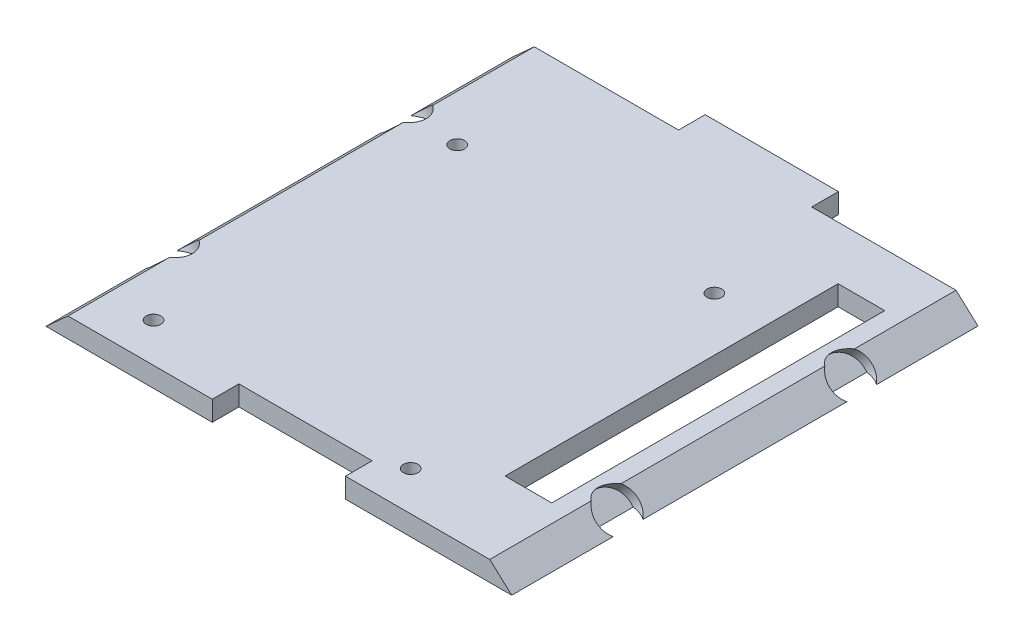
SolidWorks part; units mm, degrees
ref_plane "Front Plane" through (0, 0, 0) normal (0, 0, 1) x (1, 0, 0)
ref_plane "Top Plane" through (0, 0, 0) normal (0, 1, 0) x (1, 0, 0)
ref_plane "Right Plane" through (0, 0, 0) normal (1, 0, 0) x (0, 0, -1)
sketch "Sketch1" plane through (0, 0, 0) normal (0, 0, 1) x (1, 0, 0)
  line L0 (0, 0) -> (0, 44.45) construction
  line L1 (-40.2039, 5.9378) -> (40.2039, 5.9378)
  line L2 (-44.399, 2.1278) -> (44.399, 2.1278)
  line L3 (-40.2039, 5.9378) -> (-44.399, 2.1278)
  line L4 (40.2039, 5.9378) -> (44.399, 2.1278)
  arc A0 (44.399, 2.1278) -> (-44.399, 2.1278) centre (0, 0) ccw construction
  arc A1 (40.2039, 5.9378) -> (-40.2039, 5.9378) centre (0, 0) ccw construction
  dimension "D1" = 88.9
  dimension "D2" = 3.81
  dimension "D3" = 3.81
extrude "Boss-Extrude1" add sketch "Sketch1" along normal blind 88.9
sketch "Sketch2" plane through (0, 2.1278, 0) normal (0, -1, 0) x (1, 0, 0)
  line L0 (0, 88.9) -> (0, 0) construction
  line L1 (-34.417, 85.09) -> (20.701, 85.09) construction
  line L2 (-34.417, 85.09) -> (-34.417, 0) construction
  line L3 (-34.417, 0) -> (20.701, 0) construction
  line L4 (20.701, 85.09) -> (20.701, 0) construction
  line L5 (-44.399, 88.9) -> (44.399, 88.9) construction
  line L6 (-44.399, 0) -> (44.399, 0) construction
  line L7 (-34.417, 42.545) -> (20.701, 42.545) construction
  line L8 (-6.858, 85.09) -> (-6.858, 0) construction
  circle A0 centre (-31.369, 81.43) radius 1.397
  circle A1 centre (17.653, 23.518) radius 1.397
  circle A2 centre (-31.369, 23.518) radius 1.397
  circle A3 centre (17.653, 81.43) radius 1.397
  point P10 (-6.858, 85.09)
  dimension "D4" = 2.794
  dimension "D7" = 2.794
  dimension "D8" = 57.912
  dimension "D5" = 49.022
  dimension "D1" = 6.858
  dimension "D2" = 85.09
  dimension "D3" = 3.81
  dimension "D6" = 55.118
extrude "Cut-Extrude1" cut sketch "Sketch2" against normal through all
sketch "Sketch3" plane through (0, 2.1278, 0) normal (0, -1, 0) x (1, 0, 0)
  line L0 (0, 88.9) -> (0, 0) construction
  line L1 (-44.399, 88.9) -> (44.399, 88.9) construction
  line L2 (-44.399, 0) -> (44.399, 0) construction
  line L3 (0, 44.45) -> (44.399, 44.45) construction
  line L4 (-12.7, 88.9) -> (12.7, 88.9)
  line L5 (-12.7, 88.9) -> (-12.7, 83.82)
  line L6 (-12.7, 83.82) -> (12.7, 83.82)
  line L7 (12.7, 88.9) -> (12.7, 83.82)
  line L8 (44.399, 88.9) -> (44.399, 0) construction
  line L9 (0, 44.45) -> (-44.399, 44.45) construction
  line L10 (-44.399, 88.9) -> (-44.399, 0) construction
  line L11 (12.7, 0) -> (12.7, 5.08)
  line L12 (-12.7, 5.08) -> (12.7, 5.08)
  line L13 (-12.7, 0) -> (12.7, 0)
  line L14 (-12.7, 0) -> (-12.7, 5.08)
  point P10 (12.7, 86.36)
  dimension "D1" = 25.4
  dimension "D2" = 12.7
  dimension "D3" = 5.08
extrude "Cut-Extrude2" cut sketch "Sketch3" against normal through all
sketch "Sketch5" plane through (0, 2.1278, 0) normal (0, -1, 0) x (1, 0, 0)
  line L0 (12.7, 0) -> (12.7, 5.08) construction
  line L1 (12.7, 5.08) -> (-12.7, 5.08)
  line L2 (12.7, 5.08) -> (12.7, -5.08)
  line L3 (12.7, -5.08) -> (-12.7, -5.08)
  line L4 (-12.7, 5.08) -> (-12.7, -5.08)
  line L5 (12.7, 5.08) -> (-12.7, 5.08) construction
  dimension "D1" = 0
  dimension "D2" = 25.4
  dimension "D3" = 10.16
extrude "Boss-Extrude3" add sketch "Sketch5" against normal blind 3.81
sketch "Sketch6" plane through (0, 2.1278, 0) normal (0, -1, 0) x (1, 0, 0)
  line L0 (12.7, 88.9) -> (44.399, 88.9) construction
  line L1 (27.889, 73.66) -> (36.779, 73.66)
  line L2 (27.889, 73.66) -> (27.889, 10.16)
  line L3 (27.889, 10.16) -> (36.779, 10.16)
  line L4 (36.779, 73.66) -> (36.779, 10.16)
  line L5 (44.399, 88.9) -> (44.399, 0) construction
  dimension "D1" = 15.24
  dimension "D2" = 7.62
  dimension "D3" = 63.5
  dimension "D4" = 8.89
extrude "Cut-Extrude3" cut sketch "Sketch6" against normal through all
sketch "Sketch7" plane through (21.1272, 23.263, 0) normal (0.6723, 0.7403, 0) x (0.7403, -0.6723, 0)
  line L0 (28.6033, -88.9) -> (28.6033, -0.0854) construction
  line L1 (31.4368, -88.9) -> (25.7698, -88.9) construction
  line L2 (25.7698, -44.45) -> (31.987, -44.45) construction
  line L3 (25.7698, -88.9) -> (25.7698, 0) construction
  circle A0 centre (28.6033, -66.7177) radius 4
  circle A1 centre (28.6033, -22.1823) radius 4
  point P12 (28.6033, -44.4927)
  dimension "D1" = 8
  dimension "D2" = 22.225
extrude "Cut-Extrude4" cut sketch "Sketch7" against normal blind 2
sketch "Sketch8" plane through (-21.1272, 23.263, 0) normal (-0.6723, 0.7403, 0) x (0.7403, 0.6723, 0)
  line L0 (-28.6033, 0) -> (-28.6033, -88.7644) construction
  line L1 (-25.7698, 0) -> (-31.4368, 0) construction
  line L2 (-25.7698, -44.45) -> (-31.4368, -44.45) construction
  line L3 (-25.7698, -88.9) -> (-25.7698, 0) construction
  line L4 (-31.4368, -88.9) -> (-31.4368, 0) construction
  circle A0 centre (-28.6033, -22.1572) radius 4
  circle A1 centre (-28.6033, -66.7428) radius 4
  point P12 (-28.6033, -44.3822)
  dimension "D1" = 8
  dimension "D2" = 22.225
extrude "Cut-Extrude5" cut sketch "Sketch8" against normal blind 2
